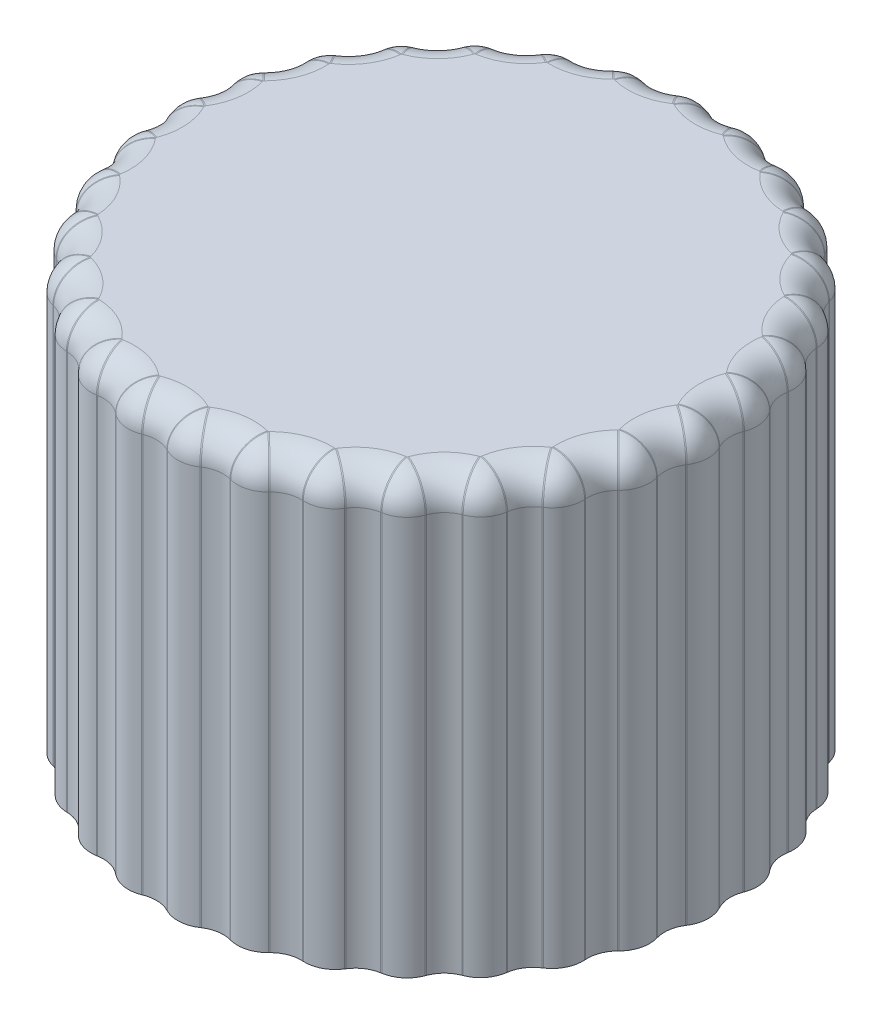
SolidWorks part; units mm, degrees
ref_plane "Ebene vorne" through (0, 0, 0) normal (0, 0, 1) x (1, 0, 0)
ref_plane "Ebene oben" through (0, 0, 0) normal (0, 1, 0) x (1, 0, 0)
ref_plane "Ebene rechts" through (0, 0, 0) normal (1, 0, 0) x (0, 0, -1)
sketch "Skizze1" plane through (0, 0, 0) normal (0, 1, 0) x (1, 0, 0)
  line L13 (7.2262, -5.7546) -> (8.5967, 3.3807)
  line L14 (8.5967, 3.3807) -> (1.3706, 9.1354)
  line L15 (1.3706, 9.1354) -> (-7.2262, 5.7546)
  line L16 (-7.2262, 5.7546) -> (-8.5967, -3.3807)
  line L17 (-8.5967, -3.3807) -> (-1.3706, -9.1354)
  line L18 (-1.3706, -9.1354) -> (7.2262, -5.7546)
  line L19 (3.2403, 8.6506) -> (-5.8715, 7.1315)
  line L20 (-5.8715, 7.1315) -> (-9.1118, -1.5191)
  line L21 (-9.1118, -1.5191) -> (-3.2403, -8.6506)
  line L22 (-3.2403, -8.6506) -> (5.8715, -7.1315)
  line L23 (5.8715, -7.1315) -> (9.1118, 1.5191)
  line L24 (9.1118, 1.5191) -> (3.2403, 8.6506)
  line L25 (-2.4644, 8.9028) -> (-8.9423, 2.3171)
  line L26 (-8.9423, 2.3171) -> (-6.4778, -6.5857)
  line L27 (-6.4778, -6.5857) -> (2.4644, -8.9028)
  line L28 (2.4644, -8.9028) -> (8.9423, -2.3171)
  line L29 (8.9423, -2.3171) -> (6.4778, 6.5857)
  line L30 (6.4778, 6.5857) -> (-2.4644, 8.9028)
  line L31 (-4.2601, 8.1966) -> (-9.2285, 0.409)
  line L32 (-9.2285, 0.409) -> (-4.9685, -7.7877)
  line L33 (-4.9685, -7.7877) -> (4.2601, -8.1966)
  line L34 (4.2601, -8.1966) -> (9.2285, -0.409)
  line L35 (9.2285, -0.409) -> (4.9685, 7.7877)
  line L36 (4.9685, 7.7877) -> (-4.2601, 8.1966)
  line L37 (-8.2649, 4.1261) -> (-7.7057, -5.0946)
  line L38 (-7.7057, -5.0946) -> (0.5592, -9.2207)
  line L39 (0.5592, -9.2207) -> (8.2649, -4.1261)
  line L40 (8.2649, -4.1261) -> (7.7057, 5.0946)
  line L41 (7.7057, 5.0946) -> (-0.5592, 9.2207)
  line L42 (-0.5592, 9.2207) -> (-8.2649, 4.1261)
  circle A0 centre (0, 0) radius 8 construction
  circle A1 centre (0, 0) radius 8 construction
  circle A2 centre (0, 0) radius 8 construction
  circle A3 centre (0, 0) radius 8 construction
  circle A4 centre (0, 0) radius 8 construction
  dimension "D1" = 16
  dimension "D2" = 16
  dimension "D3" = 16
  dimension "D4" = 16
  dimension "D5" = 16
  dimension "D6" = 1.9316
  dimension "D7" = 1.9316
  dimension "D8" = 1.9316
  dimension "D9" = 1.9316
  dimension "D10" = 1.9295
extrude "Aufsatz-Linear austragen1" add sketch "Skizze1" along normal blind 14 contours L13 L14 L15 L16 L17 L18 | L24 L19 L20 L21 L22 L23 | L42 L37 L38 L39 L40 L41 | L25 L26 L27 L28 L29 L30 | L31 L32 L33 L34 L35 L36
fillet "Verrundung1" radius 1 60 edges at (-7.2262, 7, -5.7546) (-6.2423, 7, -6.1415) (-5.8715, 7, -7.1315) (1.3706, 7, -9.1354) (2.1975, 7, -8.4768) (3.2403, 7, -8.6506) (8.5967, 7, -3.3807) (8.4399, 7, -2.3353) (9.1118, 7, -1.5191) (7.2262, 7, 5.7546) (6.2423, 7, 6.1415) (5.8715, 7, 7.1315) (-1.3706, 7, 9.1354) (-2.1975, 7, 8.4768) (-3.2403, 7, 8.6506) (-8.5967, 7, 3.3807) (-8.4399, 7, 2.3353) (-9.1118, 7, 1.5191) (8.2649, 7, 4.1261) (8.2009, 7, 3.0708) (8.9423, 7, 2.3171) (8.6605, 7, 1.2993) (9.2285, 7, 0.409) (8.741, 7, -0.5291) (7.383, 7, 4.7091) (4.8287, 7, 7.3054) (4.2601, 7, 8.1966) (3.205, 7, 8.1499) (2.4644, 7, 8.9028) (1.441, 7, 8.6376) (0.5592, 7, 9.2207) (-0.3867, 7, 8.7485) (-3.9123, 7, 7.8345) (-4.9685, 7, 7.7877) (-5.4555, 7, 6.8506) (-6.4778, 7, 6.5857) (-6.7599, 7, 5.5668) (-7.7057, 7, 5.0946) (-7.7697, 7, 4.0393) (-8.741, 7, 0.5291) (-9.2285, 7, -0.409) (-8.6605, 7, -1.2993) (-8.9423, 7, -2.3171) (-8.2009, 7, -3.0708) (-8.2649, 7, -4.1261) (-7.383, 7, -4.7091) (-4.8287, 7, -7.3054) (-4.2601, 7, -8.1966) (-3.205, 7, -8.1499) (-2.4644, 7, -8.9028) (-1.441, 7, -8.6376) (-0.5592, 7, -9.2207) (0.3867, 7, -8.7485) (3.9123, 7, -7.8345) (4.9685, 7, -7.7877) (5.4555, 7, -6.8506) (6.4778, 7, -6.5857) (6.7599, 7, -5.5668) (7.7057, 7, -5.0946) (7.7697, 7, -4.0393)
sketch "Skizze2" plane through (0, 0, 0) normal (0, -1, 0) x (1, 0, 0)
  circle A0 centre (0, 0) radius 7.5
  dimension "D1" = 15
extrude "Schnitt-Linear austragen1" cut sketch "Skizze2" against normal offset from surface (12.5 mm away) 1.5 contours A0 up to face at (0, 14, 0)
sketch "Skizze3" plane through (0, 12.5, 0) normal (0, -1, 0) x (1, 0, 0)
  line L0 (-2.4819, -1.5) -> (2.4819, -1.5)
  arc A1 (-2.4819, -1.5) -> (2.4819, -1.5) centre (0, 0) cw
  circle A2 centre (0, 0) radius 4
  dimension "D1" = 0
  dimension "D3" = 2.9
  dimension "D4" = 8
  dimension "D2" = 1.5
extrude "Aufsatz-Linear austragen2" add sketch "Skizze3" along normal offset from surface (7.5 mm away) 5 contours A2 | A1 L0 up to face at (0, 0, -7.5)
sketch "Skizze4" plane through (0, 5, 0) normal (0, -1, 0) x (1, 0, 0)
  circle A1 centre (0, 0) radius 4
extrude "Schnitt-Linear austragen3" cut sketch "Skizze4" against normal blind 0.1
sketch "Skizze5" plane through (0, 5.1, 0) normal (0, -1, 0) x (1, 0, 0)
  circle A0 centre (0, 0) radius 2.9
extrude "Schnitt-Linear austragen4" cut sketch "Skizze5" against normal blind 7.1
sketch "Skizze6" plane through (0, 5.1, 0) normal (0, -1, 0) x (1, 0, 0)
  line L1 (-0.5, 4.4686) -> (0.5, 4.4686)
  line L2 (-0.5, 4.4686) -> (-0.5, -4.8561)
  line L3 (-0.5, -4.8561) -> (0.5, -4.8561)
  line L4 (0.5, 4.4686) -> (0.5, -4.8561)
  dimension "D1" = 1
  dimension "D2" = 0.5
extrude "Schnitt-Linear austragen5" cut sketch "Skizze6" against normal up to surface (7.4 mm away) up to face at (0, 12.5, 7.5)
chamfer "Fase2" distance 0.5 angle 45 2 edges at (2.9, 5.1, 0) (-2.9, 5.1, 0)
fillet "Verrundung2" radius 1 120 edges at (6.3098, 14, 6.2079) (6.0801, 14, 6.5747) (5.7732, 14, 7.0121) (5.2849, 14, 7.2293) (4.8809, 14, 7.3843) (4.5799, 14, 7.6953) (4.1887, 14, 8.0594) (3.6666, 14, 8.1703) (3.2397, 14, 8.238) (2.881, 14, 8.4793) (2.4232, 14, 8.7537) (1.8888, 14, 8.7536) (1.4566, 14, 8.731) (1.0552, 14, 8.8927) (0.5498, 14, 9.0662) (0.0271, 14, 8.955) (-0.3909, 14, 8.843) (-0.8171, 14, 8.9177) (-1.3476, 14, 8.9824) (-1.8357, 14, 8.7649) (-2.2213, 14, 8.5684) (-2.6538, 14, 8.5528) (-3.1861, 14, 8.5058) (-3.6183, 14, 8.1915) (-3.9546, 14, 7.9191) (-4.3744, 14, 7.814) (-4.8852, 14, 7.6573) (-5.2424, 14, 7.2606) (-5.5145, 14, 6.9246) (-5.9028, 14, 6.7347) (-6.3694, 14, 6.4754) (-6.6365, 14, 6.0125) (-6.8329, 14, 5.6269) (-7.1737, 14, 5.3602) (-7.5767, 14, 5.0093) (-7.7417, 14, 4.501) (-7.8537, 14, 4.083) (-8.1316, 14, 3.7512) (-8.4528, 14, 3.3241) (-8.5085, 14, 2.7927) (-8.5311, 14, 2.3605) (-8.7339, 14, 1.9782) (-8.9592, 14, 1.4937) (-8.9032, 14, 0.9622) (-8.8355, 14, 0.5348) (-8.9543, 14, 0.1187) (-9.074, 14, -0.4021) (-8.909, 14, -0.9098) (-8.7542, 14, -1.3134) (-8.7838, 14, -1.7446) (-8.7925, 14, -2.2783) (-8.5253, 14, -2.7411) (-8.2895, 14, -3.104) (-8.2289, 14, -3.5325) (-8.1265, 14, -4.057) (-7.7689, 14, -4.454) (-7.4628, 14, -4.76) (-7.3144, 14, -5.1665) (-7.1052, 14, -5.6582) (-6.6728, 14, -5.9723) (-6.3098, 14, -6.2079) (-6.0801, 14, -6.5747) (-5.7732, 14, -7.0121) (-5.2849, 14, -7.2293) (-4.8809, 14, -7.3843) (-4.5799, 14, -7.6953) (-4.1887, 14, -8.0594) (-3.6666, 14, -8.1703) (-3.2397, 14, -8.238) (-2.881, 14, -8.4793) (-2.4232, 14, -8.7537) (-1.8888, 14, -8.7536) (-1.4566, 14, -8.731) (-1.0552, 14, -8.8927) (-0.5498, 14, -9.0662) (-0.0271, 14, -8.955) (0.3909, 14, -8.843) (0.8171, 14, -8.9177) (1.3476, 14, -8.9824) (1.8357, 14, -8.7649) (2.2213, 14, -8.5684) (2.6538, 14, -8.5528) (3.1861, 14, -8.5058) (3.6183, 14, -8.1915) (3.9546, 14, -7.9191) (4.3744, 14, -7.814) (4.8852, 14, -7.6573) (5.2424, 14, -7.2606) (5.5145, 14, -6.9246) (5.9028, 14, -6.7347) (6.3694, 14, -6.4754) (6.6365, 14, -6.0125) (6.8329, 14, -5.6269) (7.1737, 14, -5.3602) (7.5767, 14, -5.0093) (7.7417, 14, -4.501) (7.8537, 14, -4.083) (8.1316, 14, -3.7512) (8.4528, 14, -3.3241) (8.5085, 14, -2.7927) (8.5311, 14, -2.3605) (8.7339, 14, -1.9782) (8.9592, 14, -1.4937) (8.9032, 14, -0.9622) (8.8355, 14, -0.5348) (8.9543, 14, -0.1187) (9.074, 14, 0.4021) (8.909, 14, 0.9098) (8.7542, 14, 1.3134) (8.7838, 14, 1.7446) (8.7925, 14, 2.2783) (8.5253, 14, 2.7411) (8.2895, 14, 3.104) (8.2289, 14, 3.5325) (8.1265, 14, 4.057) (7.7689, 14, 4.454) (7.4628, 14, 4.76) (7.3144, 14, 5.1665) (7.1052, 14, 5.6582) (6.6728, 14, 5.9723)
